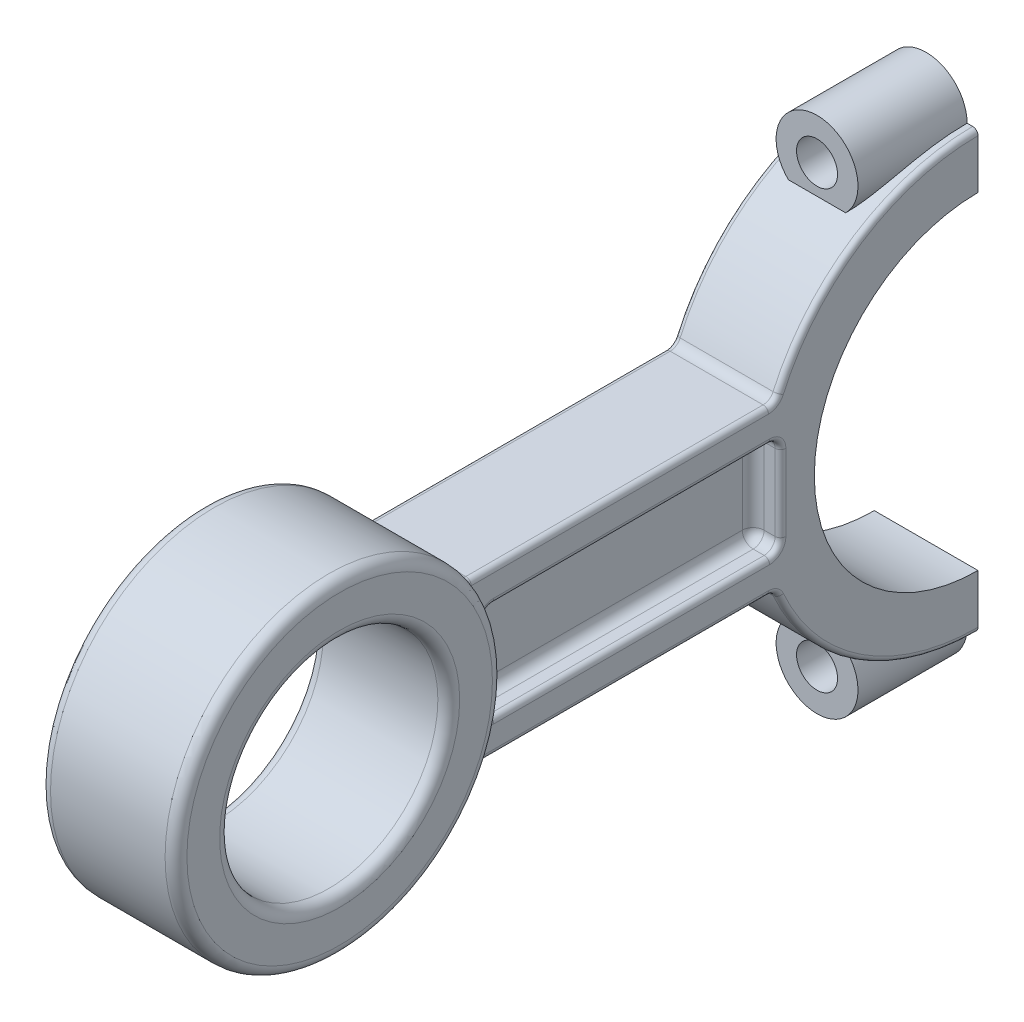
SolidWorks part; units mm, degrees
ref_plane "Front Plane" through (0, 0, 0) normal (0, 0, 1) x (1, 0, 0)
ref_plane "Top Plane" through (0, 0, 0) normal (0, 1, 0) x (1, 0, 0)
ref_plane "Right Plane" through (0, 0, 0) normal (1, 0, 0) x (0, 0, -1)
sketch "Sketch1" plane through (0, 0, 0) normal (1, 0, 0) x (0, 0, -1)
  line L0 (-76.2, 0) -> (76.2, 0) construction
  line L1 (-59.3995, 19.05) -> (29.1071, 19.05)
  line L2 (-59.3995, 19.05) -> (-59.3995, -19.05) construction
  line L3 (-59.3995, -19.05) -> (29.1071, -19.05)
  line L5 (-59.3995, 19.05) -> (59.3995, -19.05) construction
  line L6 (-59.3995, -19.05) -> (59.3995, 19.05) construction
  line L7 (76.2, -50.8) -> (76.2, -38.1)
  line L8 (76.2, 38.1) -> (76.2, 50.8)
  circle A0 centre (-76.2, 0) radius 25.4
  circle A1 centre (-76.2, 0) radius 38.1
  arc A2 (76.2, 38.1) -> (76.2, -38.1) centre (76.2, 0) ccw
  arc A3 (76.2, 50.8) -> (76.2, -50.8) centre (76.2, 0) ccw
  circle A5 centre (76.2, 0) radius 50.8 construction
  circle A6 centre (76.2, 0) radius 38.1 construction
  point P0 (0, 0)
  point P12 (112.6352, 11.1394)
  point P16 (127, 0)
  dimension "D4" = 50.8
  dimension "D1" = 76.2
  dimension "D2" = 152.4
  dimension "D3" = 38.1
  dimension "D5" = 12.7
  dimension "D6" = 12.7
extrude "Boss-Extrude2" add sketch "Sketch1" along normal mid plane 24.13 contours L1 A1 L3 A0 | L3 A1 L1 A0 | A3 L1 A1 L3 | L8 A3 L7 A2 region at (0, 0, 102.6422) region at (0, 0, 46.7377) region at (0, 0, 6.576) region at (0, 41.1793, -48.4369)
extrude "Boss-Extrude4" add sketch "Sketch1<5>" along normal mid plane 31.75 contours A1 | A0
sketch "Sketch1<5>" plane through (0, 0, 0) normal (1, 0, 0) x (0, 0, -1) same geometry as "Sketch1"
sketch "Sketch2" plane through (0, 0, -76.2) normal (0, 0, -1) x (-1, 0, 0)
  line L0 (-12.065, -50.8) -> (12.065, -50.8) construction
  circle A0 centre (0, -50.8) radius 9.525
  dimension "D1" = 19.05
extrude "Boss-Extrude5" add sketch "Sketch2" against normal blind 25.4
sketch "Sketch3" plane through (0, 0, -76.2) normal (0, 0, -1) x (-1, 0, 0)
  circle A0 centre (0, -50.8) radius 4.77
  dimension "D1" = 9.54
extrude "Cut-Extrude1" cut sketch "Sketch3" against normal blind 25.4
mirror "Mirror1" about plane through (0, 0, 0) normal (0, 1, 0) of "Boss-Extrude5", "Cut-Extrude1"
sketch "Sketch4" plane through (12.065, 0, 0) normal (1, 0, 0) x (0, 0, -1)
  line L1 (30.2187, -11.43) -> (-39.8549, -11.43)
  line L2 (30.2187, -11.43) -> (30.2187, 11.43)
  line L3 (30.2187, 11.43) -> (-39.8549, 11.43)
  line L4 (-39.8549, -11.43) -> (-39.8549, 11.43) construction
  line L5 (30.2187, -11.43) -> (-39.8549, 11.43) construction
  line L6 (30.2187, 11.43) -> (-39.8549, -11.43) construction
  line L7 (-43.2044, -19.05) -> (29.1071, -19.05) construction
  circle A0 centre (-76.2, 0) radius 38.1 construction
  arc A1 (-39.8549, -11.43) -> (-39.8549, 11.43) centre (-76.2, 0) ccw
  point P0 (-4.8181, 0)
  dimension "D2" = 7.62
extrude "Cut-Extrude2" cut sketch "Sketch4" against normal blind 6.35
mirror "Mirror2" about plane through (0, 0, 0) normal (1, 0, 0) of "Cut-Extrude2"
fillet "Fillet1" radius 2.54 24 edges at (15.875, 0, 50.8) (15.875, 0, 38.1) (-8.89, 11.43, -30.2187) (-5.715, 0, -30.2187) (-8.89, -11.43, -30.2187) (-8.89, 11.43, 39.8549) (-5.715, 0, 38.1) (-5.715, 11.43, 4.8181) (-8.89, -11.43, 39.8549) (-5.715, -11.43, 4.8181) (-15.875, 0, 50.8) (-15.875, 0, 38.1) (8.89, 11.43, 39.8549) (8.89, -11.43, 39.8549) (8.89, -11.43, -30.2187) (5.715, 0, -30.2187) (8.89, 11.43, -30.2187) (5.715, -11.43, 4.8181) (5.715, 11.43, 4.8181) (5.715, 0, 38.1) (0, -19.05, 43.2044) (0, 19.05, 43.2044) (0, -19.05, -29.1071) (0, 19.05, -29.1071)
fillet "Fillet2" radius 1.25 30 edges at (12.065, -10.4775, 38.527) (12.065, -11.43, 4.4328) (12.065, -10.6861, -29.4747) (12.065, 10.4775, 38.527) (12.065, 11.43, 4.4328) (12.065, 10.6861, -29.4747) (-12.065, -10.4775, 38.527) (-12.065, -11.43, 4.4328) (-12.065, -10.6861, -29.4747) (-12.065, 0, -30.2187) (-12.065, 10.6861, -29.4747) (-12.065, 10.4775, 38.527) (-12.065, -19.3675, 42.9989) (-12.065, -42.5746, -48.4863) (-12.065, -19.4613, -28.8104) (-12.065, 19.3675, 42.9989) (-12.065, 42.5746, -48.4863) (-12.065, 19.4613, -28.8104) (12.065, 19.3675, 42.9989) (12.065, 42.5746, -48.4863) (12.065, 19.4613, -28.8104) (12.065, -19.3675, 42.9989) (12.065, -42.5746, -48.4863) (12.065, -19.4613, -28.8104) (12.065, 0, -30.2187) (-12.065, 11.43, 4.4328) (-12.065, -19.05, 7.1722) (-12.065, 19.05, 7.1722) (12.065, 19.05, 7.1722) (12.065, -19.05, 7.1722)
